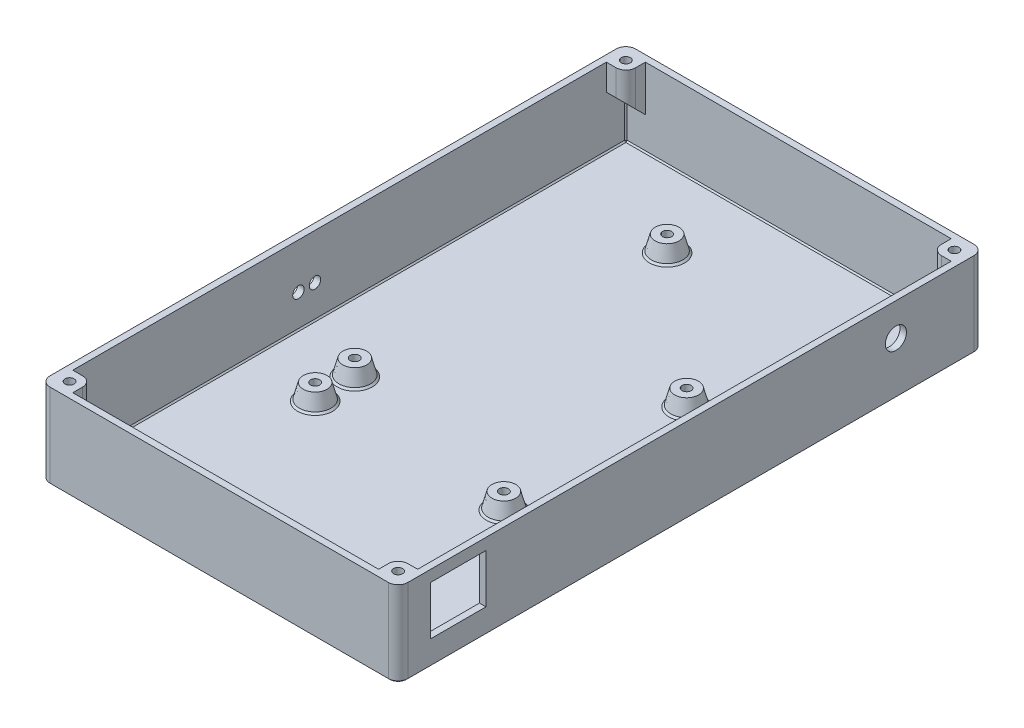
SolidWorks part; units mm, degrees
ref_plane "前视基准面" through (0, 0, 0) normal (0, 0, 1) x (1, 0, 0)
ref_plane "上视基准面" through (0, 0, 0) normal (0, 1, 0) x (1, 0, 0)
ref_plane "右视基准面" through (0, 0, 0) normal (1, 0, 0) x (0, 0, -1)
other "Configuration Table"
sketch "草图1" plane through (0, 0, 0) normal (0, 1, 0) x (1, 0, 0)
  line L1 (0, 0) -> (110, 0)
  line L2 (0, 0) -> (0, 180)
  line L3 (0, 180) -> (110, 180)
  line L4 (110, 0) -> (110, 180)
  dimension "D1" = 180
  dimension "D2" = 110
extrude "凸台-拉伸1" add sketch "草图1" along normal blind 2
sketch "草图2" plane through (0, 2, 0) normal (0, 1, 0) x (1, 0, 0)
  line L0 (0, 0) -> (110, 0) construction
  line L3 (110, 0) -> (110, 180) construction
  line L5 (110, 180) -> (0, 180) construction
  circle A0 centre (82.1, 116.57) radius 5
  circle A1 centre (38.1, 154.57) radius 5
  circle A2 centre (23.1, 73.57) radius 5
  circle A3 centre (23.5, 61) radius 5
  circle A4 centre (81.5, 61) radius 5
  circle A5 centre (81.5, 12) radius 5
  circle A6 centre (23.5, 12) radius 5
  dimension "D1" = 10
  dimension "D2" = 10
  dimension "D3" = 10
  dimension "D4" = 25.43
  dimension "D5" = 71.9
  dimension "D6" = 27.9
  dimension "D7" = 63.43
  dimension "D8" = 86.9
  dimension "D9" = 106.43
  dimension "D10" = 10
  dimension "D11" = 2
  dimension "D12" = 2
  dimension "D13" = 61
  dimension "D14" = 86.5
extrude "凸台-拉伸2" add sketch "草图2" along normal blind 5 draft 15
sketch "草图3" plane through (0, 7, 0) normal (0, 1, 0) x (1, 0, 0)
  line L0 (110, 180) -> (0, 180) construction
  line L1 (0, 180) -> (0, 0) construction
  circle A1 centre (82.1, 116.57) radius 1.4
  circle A2 centre (38.1, 154.57) radius 1.4
  circle A3 centre (23.1, 73.57) radius 1.4
  circle A4 centre (23.1, 73.57) radius 3.6603 construction
  circle A5 centre (38.1, 154.57) radius 3.6603 construction
  circle A6 centre (82.1, 116.57) radius 3.6603 construction
  circle A7 centre (18, 146) radius 1.4
  circle A11 centre (23.5, 61) radius 1.4
  circle A12 centre (81.5, 61) radius 1.4
  circle A13 centre (81.5, 12) radius 1.4
  circle A14 centre (23.5, 12) radius 1.4
  dimension "D1" = 2.8
  dimension "D2" = 2.8
  dimension "D3" = 2.8
  dimension "D4" = 0
  dimension "D5" = 0
  dimension "D6" = 0
  dimension "D7" = 0
  dimension "D8" = 0
  dimension "D9" = 0
  dimension "D10" = 2.8
  dimension "D11" = 2
  dimension "D12" = 2
  dimension "D18" = 34
  dimension "D19" = 18
extrude "切除-拉伸1" cut sketch "草图3" against normal blind 5
sketch "草图4" plane through (0, 2, 0) normal (0, 1, 0) x (1, 0, 0)
  line L9 (2, 178) -> (2, 2)
  line L10 (2, 2) -> (108, 2)
  line L11 (108, 2) -> (108, 178)
  line L12 (108, 178) -> (2, 178)
  line L13 (2, 178) -> (2, 2)
  line L14 (2, 2) -> (108, 2)
  line L15 (108, 2) -> (108, 178)
  line L16 (108, 178) -> (2, 178)
  line L21 (0, 180) -> (0, 0)
  line L22 (0, 0) -> (110, 0)
  line L23 (110, 0) -> (110, 180)
  line L24 (110, 180) -> (0, 180)
  line L25 (0, 180) -> (0, 0)
  line L26 (0, 0) -> (110, 0)
  line L27 (110, 0) -> (110, 180)
  line L28 (110, 180) -> (0, 180)
  dimension "D1" = 2
  dimension "D2" = 0
extrude "凸台-拉伸3" add sketch "草图4" along normal blind 24
sketch "草图5" plane through (0, 26, 0) normal (0, 1, 0) x (1, 0, 0)
  line L1 (2, 178) -> (8, 178)
  line L2 (2, 178) -> (2, 172)
  line L3 (2, 172) -> (8, 172)
  line L4 (8, 178) -> (8, 172)
  line L5 (108, 178) -> (102, 178)
  line L6 (108, 178) -> (108, 172)
  line L7 (108, 172) -> (102, 172)
  line L8 (102, 178) -> (102, 172)
  line L9 (108, 2) -> (102, 2)
  line L10 (108, 2) -> (108, 8)
  line L11 (108, 8) -> (102, 8)
  line L12 (102, 2) -> (102, 8)
  line L13 (2, 2) -> (8, 2)
  line L14 (2, 2) -> (2, 8)
  line L15 (2, 8) -> (8, 8)
  line L16 (8, 2) -> (8, 8)
  dimension "D1" = 6
  dimension "D2" = 6
  dimension "D3" = 6
  dimension "D4" = 6
  dimension "D5" = 6
  dimension "D6" = 6
  dimension "D7" = 6
  dimension "D8" = 6
extrude "凸台-拉伸4" add sketch "草图5" against normal blind 8
chamfer "倒角1" distance 6 angle 45 4 edges at (105, 18, -178) (5, 18, -178) (105, 18, -2) (5, 18, -2)
sketch "草图6" plane through (0, 26, 0) normal (0, 1, 0) x (1, 0, 0)
  line L0 (110, 180) -> (0, 180) construction
  line L1 (0, 180) -> (0, 0) construction
  circle A0 centre (4.5, 175.5) radius 1.4
  circle A1 centre (105.5, 175.5) radius 1.4
  circle A2 centre (105.5, 4.5) radius 1.4
  circle A3 centre (4.5, 4.5) radius 1.4
  dimension "D1" = 4.5
  dimension "D2" = 4.5
  dimension "D3" = 2.8
  dimension "D4" = 2
  dimension "D5" = 2
extrude "切除-拉伸2" cut sketch "草图6" against normal blind 8
fillet "圆角1" radius 3 8 edges at (0, 13, 0) (110, 13, 0) (110, 13, -180) (0, 13, -180) (102, 22, -8) (102, 22, -172) (8, 22, -8) (8, 22, -172)
chamfer "倒角2" distance 0.4 angle 45 8 edges at (109.1213, 0, -0.8787) (110, 0, -90) (109.1213, 0, -179.1213) (55, 0, -180) (0.8787, 0, -179.1213) (0, 0, -90) (0.8787, 0, -0.8787) (55, 0, 0)
chamfer "倒角3" distance 0.4 angle 45 15 edges at (82.1, 2, -121.57) (38.1, 2, -159.57) (23.1, 2, -78.57) (108, 7, -2) (108, 2, -90) (108, 7, -178) (55, 2, -178) (55, 2, -2) (2, 7, -2) (2, 2, -90) (2, 7, -178) (23.5, 2, -66) (81.5, 2, -66) (81.5, 2, -17) (23.5, 2, -17) first distance on face at (55, 2, -90) first distance on face at (108, 14.5, -90) first distance on face at (2, 14.5, -90)
sketch "草图9" plane through (108, 0, 0) normal (-1, 0, 0) x (0, 0, 1)
  line L0 (-8, 26) -> (-172, 26) construction
  circle A0 centre (-153, 16) radius 3.25
  point P4 (-90, 26)
  dimension "D1" = 6.5
  dimension "D2" = 10
  dimension "D3" = 63
extrude "切除-拉伸4" cut sketch "草图9" against normal blind 10
sketch "草图10" plane through (2, 0, 0) normal (1, 0, 0) x (0, 0, -1)
  line L0 (3, 26) -> (177, 26) construction
  line L1 (2, 2.4) -> (2, 12) construction
  circle A0 centre (82.43, 12.1) radius 1.75
  circle A1 centre (77.35, 12.1) radius 1.75
  dimension "D1" = 3.5
  dimension "D2" = 3.5
  dimension "D3" = 13.9
  dimension "D4" = 13.9
  dimension "D5" = 5.08
  dimension "D6" = 75.35
extrude "切除-拉伸5" cut sketch "草图10" against normal blind 10
sketch "草图11" plane through (108, 0, 0) normal (-1, 0, 0) x (0, 0, 1)
  line L0 (-8, 26) -> (-172, 26) construction
  line L1 (-27, 22.5) -> (-10, 22.5)
  line L2 (-27, 22.5) -> (-27, 7.5)
  line L3 (-27, 7.5) -> (-10, 7.5)
  line L4 (-10, 22.5) -> (-10, 7.5)
  line L5 (0, 0.4) -> (0, 26) construction
  dimension "D1" = 17
  dimension "D2" = 15
  dimension "D3" = 3.5
  dimension "D4" = 10
extrude "切除-拉伸6" cut sketch "草图11" against normal blind 10
equation "\"D6@草图10\"=15.35+60"
